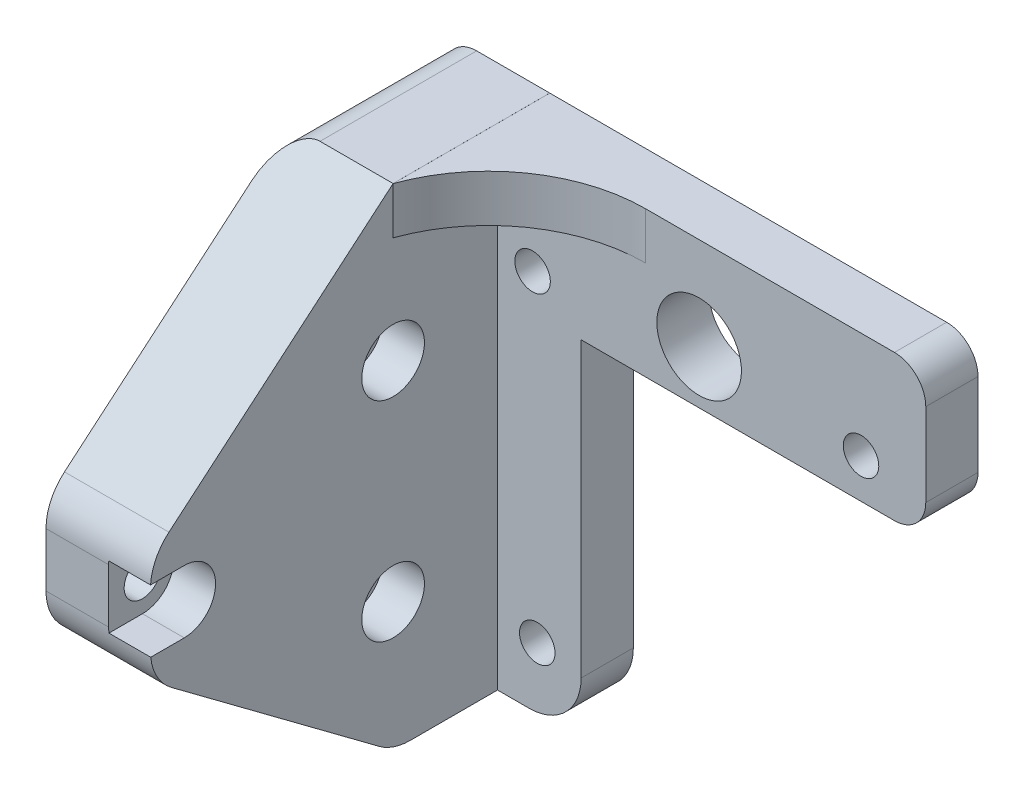
SolidWorks part; units mm, degrees
material "ABS"
ref_plane "Front Plane" through (0, 0, 0) normal (0, 0, 1) x (1, 0, 0)
ref_plane "Top Plane" through (0, 0, 0) normal (0, 1, 0) x (1, 0, 0)
ref_plane "Right Plane" through (0, 0, 0) normal (1, 0, 0) x (0, 0, -1)
ref_plane "Plane5" through (60, 0, 0) normal (1, 0, 0) x (0, 0, -1)
sketch "Sketch50" plane through (60, 0, 0) normal (1, 0, 0) x (0, 0, -1)
  line L0 (-38.2349, -28) -> (-38.2349, -38)
  line L1 (0, -55.3249) -> (-15, -55.3249)
  line L2 (0, -8.3249) -> (-15, -8.3249)
  line L4 (0, -55.3249) -> (0, -8.3249)
  line L5 (-15, -2.0171) -> (-15, -57.8143) construction
  line L9 (-38.2349, -28) -> (-15, -8.3249)
  line L10 (-38.2349, -38) -> (-15, -55.3249)
  circle A0 centre (-35, -33) radius 1.75
  circle A1 centre (-15, -23) radius 1.75
  circle A2 centre (-15, -43) radius 1.75
  dimension "D1" = 3.5
  dimension "D2" = 3.5
  dimension "D3" = 3.5
  dimension "D4" = 20
  dimension "D5" = 20
  dimension "D6" = 47
  dimension "D7" = 15
  dimension "D8" = 10
extrude "Extrude1" add sketch "Sketch50" along normal blind 10 separate body
sketch "Sketch52" plane through (0, 0, 0) normal (0, 0, -1) x (-1, 0, 0)
  line L0 (-60.0211, -55.3284) -> (-60.0211, -8.3284)
  line L1 (-111, -8.3284) -> (-111, -22.2806)
  line L2 (-60.0211, -8.3284) -> (-111, -8.3284)
  line L3 (-78, -22.2806) -> (-111, -22.2806)
  line L4 (-60.0211, -55.3284) -> (-78, -55.3284)
  line L5 (-78, -55.3249) -> (-78, -8.3249)
  line L6 (-78, -55.3284) -> (-78, -22.2806)
  circle A0 centre (-89.3, -17.2) radius 4.05
  circle A1 centre (-73.3515, -18.9313) radius 1.7
  circle A2 centre (-104.8, -18.5) radius 1.7
  circle A3 centre (-73.8015, -49.5086) radius 1.7
  point P3 (-113, -87.5802)
  point P9 (-74.0211, -54.9585)
  point P10 (-74.0211, -7.7617)
  dimension "D2" = 47
  dimension "D4" = 3.4
  dimension "D1" = 8
extrude "Extrude2" add sketch "Sketch52" against normal blind 5
fillet "Fillet1" radius 3 2 edges at (111, -22.2806, 2.5) (111, -8.3284, 2.5)
fillet "Fillet2" radius 5 1 edges at (78, -55.3284, 2.5)
sketch "Sketch54" plane through (0, -8.3284, 0) normal (0, 1, 0) x (1, 0, 0)
  line L0 (70, -5) -> (108, -5) construction
  line L1 (70, -15.0014) -> (70, -5)
  line L3 (70, 0) -> (70, -15) construction
  line L4 (70, -5) -> (84.1795, -5)
  arc A0 (84.1795, -5) -> (70, -15.0014) centre (84.1795, -20.0521) ccw
extrude "Extrude3" add sketch "Sketch54" against normal blind 4.5
fillet "Fillet4" radius 5 3 edges at (65, -28, 38.2349) (65, -38, 38.2349) (65, -55.3249, 15)
fillet "Fillet5" radius 3 1 edges at (60, -8.3249, 7.5)
sketch "Sketch55" plane through (70, 0, 0) normal (1, 0, 0) x (0, 0, -1)
  line L0 (-35, -30) -> (-38.7879, -30)
  line L1 (-38.7879, -30) -> (-38.7879, -36)
  line L2 (-35, -36) -> (-38.7879, -36)
  arc A0 (-35, -36) -> (-35, -30) centre (-35, -33) ccw
  circle A1 centre (-15, -23) radius 3
  circle A2 centre (-15, -43) radius 3
  dimension "D1" = 6
  dimension "D2" = 6
  dimension "D3" = 6
extrude "Cut-Extrude3" cut sketch "Sketch55" against normal blind 4
